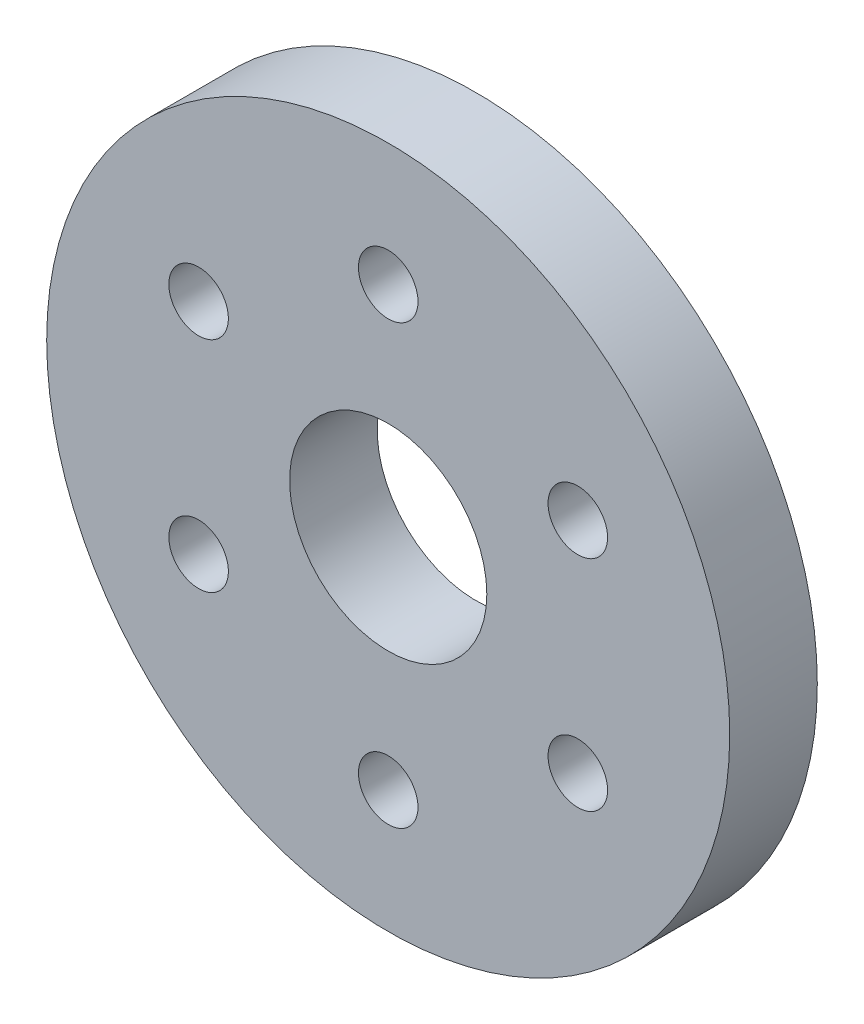
SolidWorks part; units mm, degrees
material "Markforged"
ref_plane "Front Plane" through (0, 0, 0) normal (0, 0, 1) x (1, 0, 0)
ref_plane "Top Plane" through (0, 0, 0) normal (0, 1, 0) x (1, 0, 0)
ref_plane "Right Plane" through (0, 0, 0) normal (1, 0, 0) x (0, 0, -1)
sketch "Sketch1" plane through (0, 0, 0) normal (0, 0, 1) x (1, 0, 0)
  line L0 (0, 0) -> (0, 24.765) construction
  circle A0 centre (0, 0) radius 24.765
  circle A1 centre (0, 0) radius 7.1501
  dimension "D1" = 49.53
  dimension "D2" = 14.3002
extrude "Boss-Extrude2" add sketch "Sketch1" along normal blind 6.35
sketch "Sketch3" plane through (0, 0, 6.35) normal (0, 0, 1) x (1, 0, 0)
  line L0 (0, 7.1501) -> (0, 24.765) construction
  circle A0 centre (0, 0) radius 7.1501 construction
  circle A1 centre (0, 0) radius 24.765 construction
  circle A2 centre (0, 15.875) radius 2.159
  dimension "D1" = 4.318
  dimension "D2" = 15.875
extrude "Cut-Extrude3" cut sketch "Sketch3" against normal through all both and the other way through all
pattern_circular "CirPattern1" count 6 over 360 about axis through (0, 0, 6.35) along (0, 0, 1) of "Cut-Extrude3"
